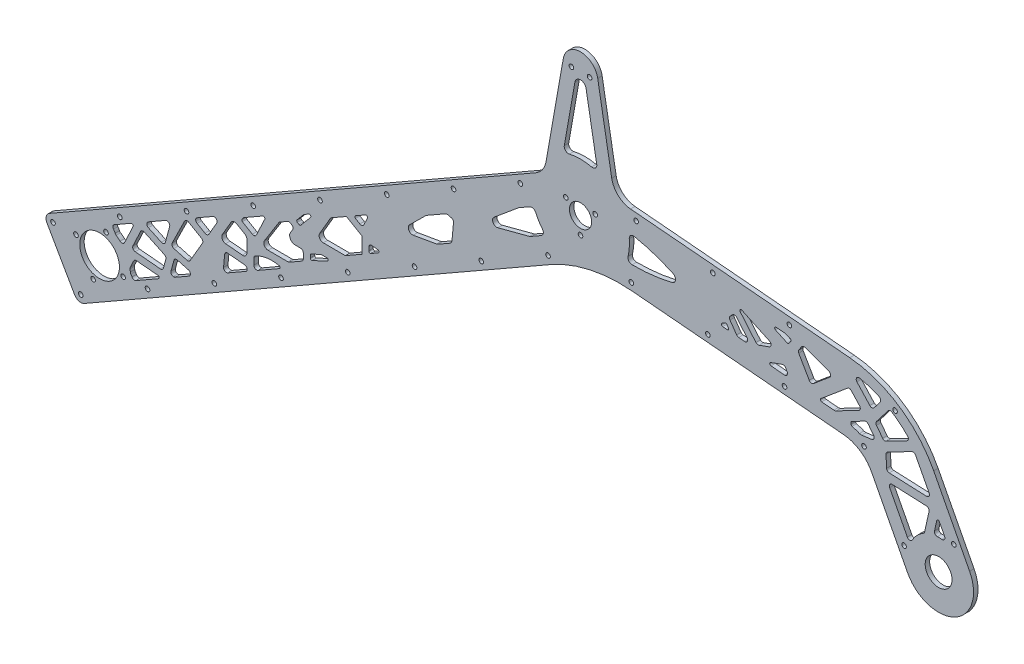
SolidWorks part; units mm, degrees
material "6061-T6 (SS)"
ref_plane "Front Plane" through (0, 0, 0) normal (0, 0, 1) x (1, 0, 0)
ref_plane "Top Plane" through (0, 0, 0) normal (0, 1, 0) x (1, 0, 0)
ref_plane "Right Plane" through (0, 0, 0) normal (1, 0, 0) x (0, 0, -1)
sketch "Reference Sketch" plane through (0, 0, 0) normal (0, 0, 1) x (1, 0, 0)
  line L0 (-343.92, -196.825) -> (0, 0) construction
  line L1 (-243.92, 103.175) -> (356.08, 103.175) construction
  line L2 (-243.92, 103.175) -> (-243.92, 0) construction
  line L3 (-243.92, 0) -> (356.08, 0) construction
  line L4 (356.08, 103.175) -> (356.08, 0) construction
  line L5 (0, 0) -> (256.08, -92.7116) construction
  line L6 (256.08, -92.7116) -> (56.08, -196.825) construction
  line L7 (256.08, -92.7116) -> (456.08, -196.825) construction
  line L8 (-343.92, -196.825) -> (56.08, -196.825) construction
  line L9 (56.08, -196.825) -> (456.08, -196.825) construction
  circle A1 centre (-343.92, -196.825) radius 100 construction
  circle A2 centre (56.08, -196.825) radius 100 construction
  circle A3 centre (456.08, -196.825) radius 100 construction
  circle A4 centre (-343.92, -196.825) radius 16.05 construction
  circle A5 centre (-343.92, -196.825) radius 28.55 construction
  circle A6 centre (-343.92, -196.825) radius 38.55 construction
  circle A7 centre (-343.92, -196.825) radius 33.55 construction
  point P13 (-343.92, -296.825)
  point P14 (556.08, -196.825)
  point P17 (-443.92, -196.825)
  dimension "D3" = 32.1
  dimension "D5" = 200
  dimension "D9" = 57.1
  dimension "D10" = 10
  dimension "D11" = 5
  dimension "D1" = 600
  dimension "D2" = 103.175
  dimension "D4" = 243.92
  dimension "D6" = 125
  dimension "D7" = 400
  dimension "D8" = 1000
  dimension "D12" = 356.08
sketch "Sketch2" plane through (0, 0, 0) normal (0, 0, 1) x (1, 0, 0)
  line L0 (-379.7168, -188.5069) -> (-32.0065, 10.4873)
  line L1 (-354.8814, -231.9028) -> (-21.5627, -41.1449)
  line L2 (-343.92, -196.825) -> (0, 0) construction
  line L3 (-184.3777, -76.7146) -> (-159.5423, -120.1104) construction
  line L4 (-24.685, 20.9013) -> (-12.3101, 91.0831)
  line L5 (12.3101, 91.0831) -> (22.322, 34.3028)
  line L6 (0, 98.4125) -> (0, 112.7) construction
  line L7 (-5.4848, 79.4125) -> (5.4848, 79.4125) construction
  line L8 (5.4848, 79.4125) -> (10.9697, 88.9125) construction
  line L9 (10.9697, 88.9125) -> (5.4848, 98.4125) construction
  line L10 (5.4848, 98.4125) -> (-5.4848, 98.4125) construction
  line L11 (-5.4848, 98.4125) -> (-10.9697, 88.9125) construction
  line L12 (-10.9697, 88.9125) -> (-5.4848, 79.4125) construction
  line L13 (-243.92, 103.175) -> (356.08, 103.175) construction
  line L14 (0, 88.9125) -> (0, 0) construction
  line L15 (35.7868, 21.9646) -> (192.5861, 8.2464)
  line L16 (252.5753, -31.8371) -> (278.2553, -81.1679)
  line L17 (233.9047, -104.2553) -> (208.2247, -54.9245)
  line L18 (36.8237, -28.3172) -> (188.2284, -41.5633)
  line L19 (0, 0) -> (192.5861, -16.8491) construction
  line L21 (-360.8064, -192.2315) -> (-339.3265, -179.9386) construction
  line L22 (-381.5729, -195.33) -> (-361.7045, -230.0467)
  line L23 (256.08, -92.7116) -> (56.08, -196.825) construction
  line L25 (-243.92, 0) -> (356.08, 0) construction
  circle A0 centre (0, 0) radius 7.9375
  circle A1 centre (-343.92, -196.825) radius 14.2
  arc A3 (-12.3101, 91.0831) -> (12.3101, 91.0831) centre (0, 88.9125) cw
  circle A4 centre (0, 88.9125) radius 6.5 construction
  circle A5 centre (-6.5, 88.9125) radius 1.65
  circle A6 centre (6.5, 88.9125) radius 1.65
  circle A7 centre (0, 88.9125) radius 9.5 construction
  arc A8 (252.5753, -31.8371) -> (192.5861, 8.2464) centre (186.0495, -66.4682) ccw
  circle A9 centre (256.08, -92.7116) radius 9.5885
  arc A10 (278.2553, -81.1679) -> (233.9047, -104.2553) centre (256.08, -92.7116) cw
  arc A11 (-21.5627, -41.1449) -> (36.8237, -28.3172) centre (28.1082, -127.9366) cw
  arc A12 (188.2284, -41.5633) -> (208.2247, -54.9245) centre (186.0495, -66.4682) cw
  arc A13 (22.322, 34.3028) -> (35.7868, 21.9646) centre (37.0941, 36.9075) ccw
  arc A14 (-32.0065, 10.4873) -> (-24.685, 20.9013) centre (-39.4572, 23.506) ccw
  circle A17 centre (-343.92, -196.825) radius 17.5 construction
  circle A18 centre (-360.8064, -192.2315) radius 1.65
  circle A19 centre (-339.3265, -179.9386) radius 1.65
  circle A20 centre (-327.0336, -201.4185) radius 1.65
  circle A21 centre (-348.5135, -213.7114) radius 1.65
  arc A27 (-379.7168, -188.5069) -> (-381.5729, -195.33) centre (-377.2333, -192.8465) ccw
  arc A28 (-361.7045, -230.0467) -> (-354.8814, -231.9028) centre (-357.3649, -227.5632) ccw
  circle A29 centre (-343.92, -196.825) radius 33.55 construction
  circle A32 centre (-343.92, -196.825) radius 38.55 construction
  point P16 (-171.96, -98.4125)
  point P64 (-343.92, -196.825)
  dimension "D1" = 15.875
  dimension "D2" = 28.4
  dimension "D3" = 35
  dimension "D5" = 13
  dimension "D6" = 3.3
  dimension "D7" = 6
  dimension "D12" = 50
  dimension "D14" = 100
  dimension "D16" = 15
  dimension "D17" = 5
  dimension "D18" = 25
  dimension "D19" = 3.3
  dimension "D15" = 4
  dimension "D20" = 19.177
  dimension "D4" = 50
  dimension "D8" = 19
  dimension "D9" = 14.2875
  dimension "D10" = 9.525
  dimension "D11" = 10
  dimension "D13" = 50
extrude "Base" add sketch "Sketch2" along normal blind 3.175
sketch "Sketch3" plane through (0, 0, 3.175) normal (0, 0, 1) x (1, 0, 0)
  line L0 (-343.92, -196.825) -> (0, 0) construction
  line L5 (0, 0) -> (197.3986, -17.2701) construction
  line L6 (192.5861, 8.2464) -> (35.7868, 21.9646) construction
  line L7 (0, 0) -> (-23.2167, -36.3305) construction
  line L8 (36.3074, -23.2529) -> (91.0981, -28.0464) construction
  line L9 (36.8237, -28.3172) -> (188.2284, -41.5633) construction
  line L10 (-357.3649, -227.5632) -> (-309.6295, -200.2442) construction
  line L11 (0, 0) -> (36.3074, -23.2529) construction
  line L12 (145.8888, -32.84) -> (188.6641, -36.5824) construction
  line L13 (149.375, 7.0078) -> (192.1504, 3.2654) construction
  line L14 (248.1402, -34.1458) -> (266.894, -70.1715) construction
  line L15 (278.2553, -81.1679) -> (252.5753, -31.8371) construction
  line L16 (212.6598, -52.6158) -> (231.4136, -88.6414) construction
  line L17 (208.2247, -54.9245) -> (233.9047, -104.2553) construction
  line L18 (231.4136, -88.6414) -> (266.894, -70.1715) construction
  circle A0 centre (-357.3649, -227.5632) radius 1.65
  circle A1 centre (-343.92, -196.825) radius 33.55 construction
  arc A2 (-361.7045, -230.0467) -> (-354.8814, -231.9028) centre (-357.3649, -227.5632) ccw construction
  circle A3 centre (-309.6295, -200.2442) radius 1.65
  circle A4 centre (-261.894, -172.9253) radius 1.65
  circle A5 centre (-214.1585, -145.6063) radius 1.65
  circle A6 centre (-166.4231, -118.2874) radius 1.65
  circle A7 centre (-118.6876, -90.9684) radius 1.65
  circle A8 centre (-329.4978, -165.5275) radius 1.65
  circle A9 centre (-377.2333, -192.8465) radius 1.65
  circle A10 centre (-281.7623, -138.2086) radius 1.65
  circle A11 centre (-234.0269, -110.8896) radius 1.65
  circle A12 centre (-186.2914, -83.5707) radius 1.65
  circle A13 centre (-138.5559, -56.2517) radius 1.65
  circle A14 centre (36.3074, -23.2529) radius 1.65
  circle A15 centre (91.0981, -28.0464) radius 1.65
  circle A16 centre (145.8888, -32.84) radius 1.65
  circle A17 centre (149.375, 7.0078) radius 1.65
  circle A18 centre (94.5843, 11.8013) radius 1.65
  circle A19 centre (39.7936, 16.5949) radius 1.65
  circle A20 centre (-70.9521, -63.6495) radius 1.65
  circle A21 centre (-23.2167, -36.3305) radius 1.65
  circle A22 centre (-43.085, -1.6138) radius 1.65
  circle A23 centre (-90.8205, -28.9328) radius 1.65
  arc A24 (188.6641, -36.5824) -> (212.6598, -52.6158) centre (186.0495, -66.4682) cw construction
  arc A25 (208.2247, -54.9245) -> (188.2284, -41.5633) centre (186.0495, -66.4682) ccw construction
  circle A26 centre (202.7166, -41.5241) radius 1.65
  arc A27 (192.1504, 3.2654) -> (248.1402, -34.1458) centre (186.0495, -66.4682) cw construction
  arc A28 (252.5753, -31.8371) -> (192.5861, 8.2464) centre (186.0495, -66.4682) ccw construction
  circle A29 centre (224.9394, -8.2653) radius 1.65
  circle A30 centre (231.4136, -88.6414) radius 1.65
  circle A31 centre (266.894, -70.1715) radius 1.65
  circle A32 centre (256.08, -92.7116) radius 9.5885 construction
  point P82 (263.5112, -63.6495)
  dimension "D1" = 3.3
  dimension "D2" = 8
  dimension "D3" = 5
  dimension "D5" = 3
  dimension "D6" = 15
  dimension "D4" = 55
extrude "Strut Holes" cut sketch "Sketch3" against normal through all
sketch "Sketch6" plane through (0, 0, 3.175) normal (0, 0, 1) x (1, 0, 0)
  line L0 (-317.9371, -199.2378) -> (-301.7593, -189.9792)
  line L1 (-354.8814, -231.9028) -> (-21.5627, -41.1449) construction
  line L2 (-289.845, -183.1607) -> (-279.9388, -177.4914)
  line L3 (-225.0683, -146.089) -> (-215.3943, -140.5526)
  line L4 (-202.4502, -105.5293) -> (-201.3111, -106.1928)
  line L5 (-333.4446, -172.395) -> (-321.3247, -165.4588)
  line L6 (-32.0065, 10.4873) -> (-379.7168, -188.5069) construction
  line L7 (-319.9233, -166.7528) -> (-326.0767, -179.819)
  line L8 (-329.2222, -183.6702) -> (-327.9453, -183.7868) construction
  line L9 (-302.165, -188.1154) -> (-317.5291, -186.7124)
  line L10 (-319.5204, -187.852) -> (-321.9207, -192.9489)
  line L11 (-296.5261, -175.2812) -> (-298.2962, -181.7883)
  line L12 (-300.4079, -183.2551) -> (-318.4265, -181.6097)
  line L13 (-320.054, -178.7659) -> (-314.5879, -167.159)
  line L14 (-311.9264, -166.2018) -> (-297.6038, -172.9468)
  line L15 (-280.4073, -173.8257) -> (-288.2923, -171.6808)
  line L16 (-290.7472, -173.0857) -> (-292.8686, -180.8843)
  line L17 (-296.7252, -151.3805) -> (-309.1621, -158.4982)
  line L18 (-309.0208, -162.0434) -> (-299.7125, -166.427)
  line L19 (-296.9305, -165.1426) -> (-293.8019, -153.6413)
  line L20 (-290.7492, -165.8308) -> (-281.4187, -168.3689)
  line L21 (-279.1655, -167.4456) -> (-270.335, -152.2839)
  line L22 (-271.0566, -149.5491) -> (-280.339, -144.1428)
  line L23 (-283.1398, -144.9875) -> (-292.0185, -163.0173)
  line L24 (-274.1749, -138.475) -> (-262.8296, -131.9821)
  line L25 (-260.108, -134.7245) -> (-265.8054, -144.5068)
  line L26 (-268.5402, -145.2285) -> (-274.188, -141.9391)
  line L27 (-255.2613, -159.7424) -> (-254.4886, -151.2802)
  line L28 (-252.315, -149.4703) -> (-240.2297, -150.5739)
  line L29 (-292.2711, -190.3101) -> (-299.0066, -188.4038) construction
  line L30 (-252.2762, -161.6601) -> (-239.4181, -154.3014)
  line L31 (-249.9491, -129.2039) -> (-256.1296, -139.8156)
  line L32 (-253.8101, -144.313) -> (-241.8428, -145.4058)
  line L33 (-238.5701, -142.4296) -> (-238.5385, -134.1139)
  line L34 (-240.0286, -131.5101) -> (-245.8469, -128.1214)
  line L35 (-233.5719, -142.9305) -> (-233.588, -147.1604)
  line L36 (-241.7536, -124.7193) -> (-234.6398, -128.8625)
  line L37 (-231.8238, -127.9864) -> (-225.7969, -115.1887)
  line L38 (-227.1983, -113.8948) -> (-240.4869, -121.4998)
  line L39 (-215.7001, -112.1928) -> (-226.033, -128.59)
  line L40 (-223.5063, -133.1894) -> (-209.2023, -133.2437)
  line L41 (-208.2012, -132.9795) -> (-199.2535, -127.8588)
  line L42 (-198.247, -126.1305) -> (-198.2324, -122.2852)
  line L43 (-200.2248, -120.2776) -> (-204.0086, -120.2632)
  line L44 (-207.3776, -114.1307) -> (-205.8611, -111.7242)
  line L45 (-206.5466, -108.9297) -> (-207.4931, -108.3784)
  line L46 (-209.4931, -108.3708) -> (-215.0015, -111.5233)
  line L47 (-220.5938, -138.2005) -> (-191.3457, -138.3115) construction
  line L48 (-200.0442, -105.9743) -> (-193.1087, -97.7724)
  line L49 (-194.3691, -96.2588) -> (-197.5103, -98.0565)
  line L50 (-198.0441, -98.501) -> (-202.7105, -104.0195)
  line L51 (-193.2277, -121.0545) -> (-193.2345, -122.8478)
  line L52 (-191.8153, -123.7595) -> (-180.9934, -118.7631)
  line L54 (-192.6468, -120.1504) -> (-185.8787, -117.0256)
  line L55 (-185.0328, -116.8414) -> (-181.4088, -116.8552)
  line L56 (-168.149, -108.9055) -> (-183.9527, -108.8455)
  line L57 (-186.5337, -104.3356) -> (-178.5799, -90.6792)
  line L58 (-178.5799, -90.6792) -> (-167.3868, -84.2735)
  line L59 (-167.3868, -84.2735) -> (-156.3884, -90.6792)
  line L60 (-156.3884, -90.6792) -> (-156.4321, -102.1999)
  line L61 (-156.4321, -102.1999) -> (-168.149, -108.9055)
  line L62 (-178.5799, -90.6792) -> (-168.149, -108.9055) construction
  line L63 (-151.4146, -97.6001) -> (-151.4054, -95.1814)
  line L64 (-149.2236, -93.1973) -> (-145.0326, -93.58)
  line L65 (-144.6268, -95.4437) -> (-149.9179, -98.4719)
  line L66 (-160.8726, -80.5454) -> (-153.7619, -76.4759)
  line L67 (-152.3605, -77.7699) -> (-154.93, -83.2262)
  line L68 (-157.746, -84.1023) -> (-160.8792, -82.2774)
  line L69 (-155.8599, -85.2008) -> (-151.3971, -92.9988) construction
  line L70 (-90.8199, -49.6985) -> (-91.8964, -61.4879)
  line L71 (-93.3939, -63.8188) -> (-101.9943, -68.7409)
  line L72 (-102.9747, -69.0935) -> (-119.6299, -71.9651)
  line L73 (-122.2529, -66.8794) -> (-110.6811, -55.3952)
  line L74 (-110.058, -54.9208) -> (-96.7247, -47.2901)
  line L75 (-94.4471, -46.9991) -> (-92.2866, -47.5868)
  line L76 (-102.4534, -69.0036) -> (-110.4008, -55.117) construction
  line L78 (-28.0968, -26.4494) -> (-35.8254, -30.8725)
  line L79 (-36.5501, -31.1694) -> (-59.134, -37.129)
  line L80 (-61.819, -31.9228) -> (-44.3172, -17.3499)
  line L81 (-43.8877, -17.0516) -> (-36.2746, -12.6946)
  line L82 (-44.1155, -17.182) -> (-36.1682, -31.0687) construction
  line L83 (-11.5997, 37.5245) -> (-3.9861, 80.7029)
  line L84 (3.9861, 80.7029) -> (11.5997, 37.5245)
  line L85 (22.322, 34.3028) -> (12.3101, 91.0831) construction
  line L86 (-12.3101, 91.0831) -> (-24.685, 20.9013) construction
  line L87 (192.5861, 8.2464) -> (35.7868, 21.9646) construction
  line L88 (36.8237, -28.3172) -> (188.2284, -41.5633) construction
  line L89 (-227.1773, -153.057) -> (-233.9128, -151.1507) construction
  line L90 (246.076, -72.9136) -> (249.254, -58.5784)
  line L91 (247.3887, -56.1475) -> (222.9622, -55.081)
  line L92 (221.1009, -58.0026) -> (233.7353, -82.273)
  line L93 (208.2247, -54.9245) -> (233.9047, -104.2553) construction
  line L94 (253.1337, -68.7997) -> (254.752, -61.5)
  line L95 (256.6153, -61.2547) -> (260.3456, -68.4206)
  line L96 (278.2553, -81.1679) -> (252.5753, -31.8371) construction
  line L97 (249.3108, -47.2228) -> (239.5975, -28.5637)
  line L98 (236.9, -27.7132) -> (219.5656, -36.7369)
  line L99 (218.491, -38.5982) -> (218.8608, -47.0688)
  line L100 (220.7717, -48.9796) -> (247.4495, -50.1444)
  line L101 (233.4135, -22.7639) -> (218.6181, -30.4658)
  line L102 (216.1079, -29.9093) -> (211.6718, -24.1281)
  line L103 (211.6718, -21.693) -> (220.0072, -10.8302)
  line L104 (209.6166, -31.3057) -> (205.7463, -26.2618)
  line L105 (203.2361, -25.7053) -> (194.0101, -30.5081)
  line L106 (193.4718, -31.3951) -> (193.4718, -32.4967)
  line L107 (201.069, -35.4569) -> (208.2909, -34.5061)
  line L108 (214.3031, -8.4078) -> (209.9577, -14.0708)
  line L109 (197.6887, -4.156) -> (206.8964, -14.2045)
  line L110 (193.6814, -11.6243) -> (199.5455, -18.0239)
  line L111 (198.9945, -21.1491) -> (182.8075, -29.5754)
  line L112 (181.1608, -29.903) -> (172.4826, -29.1438)
  line L113 (171.927, -27.3815) -> (190.9213, -11.4434)
  line L114 (178.1992, -11.0225) -> (166.5918, -20.7623)
  line L115 (163.5742, -20.2302) -> (156.048, -7.1944)
  line L116 (156.1417, -5.0472) -> (158.1885, -2.1242)
  line L117 (160.5108, -1.3919) -> (177.5977, -7.611)
  line L118 (146.6448, -20.9077) -> (147.747, -22.8167)
  line L119 (145.8406, -25.8091) -> (136.23, -24.9682)
  line L120 (135.9751, -23.0324) -> (144.2287, -20.0283)
  line L121 (134.9743, -13.819) -> (127.6718, -16.4769)
  line L122 (125.4557, -15.8831) -> (114.1985, -2.4673)
  line L123 (115.3872, -0.9182) -> (135.1355, -10.127)
  line L124 (139.4306, -1.096) -> (147.8318, -5.0136)
  line L125 (149.0736, -4.6809) -> (150.4259, -2.7496)
  line L126 (149.9488, -1.2363) -> (146.0985, 0.1651)
  line L127 (145.3339, 0.3346) -> (139.9404, 0.8065)
  line L128 (111.6605, -7.2212) -> (119.0455, -16.0223)
  line L129 (117.3391, -19.3002) -> (113.1162, -18.9308)
  line L130 (111.6522, -18.0855) -> (106.8775, -11.2665)
  line L131 (107.1016, -8.7052) -> (108.7142, -7.0926)
  line L132 (104.7039, -15.1361) -> (105.7554, -16.6377)
  line L133 (104.8491, -18.2075) -> (101.6773, -17.93)
  line L134 (101.2644, -16.0678) -> (103.3847, -14.8436)
  line L135 (-225.0683, -146.089) -> (-230.5959, -149.2525)
  line L136 (-233.5893, -147.5091) -> (-233.588, -147.1604)
  arc A0 (-320.7312, -198.3723) -> (-321.5152, -197.1118) centre (-327.0336, -201.4185) ccw
  arc A1 (-291.1568, -183.3993) -> (-291.2348, -183.3872) centre (-292.2711, -190.3101) ccw
  arc A2 (-225.7665, -146.2006) -> (-231.9116, -147.9008) centre (-227.1773, -153.057) ccw construction
  arc A4 (-321.937, -195.96) -> (-322.0953, -194.053) centre (-343.92, -196.825) ccw
  arc A5 (-332.8179, -177.3623) -> (-333.9791, -175.4215) centre (-339.3265, -179.9386) ccw
  arc A6 (-329.2222, -180.455) -> (-332.0384, -178.3094) centre (-343.92, -196.825) ccw
  arc A8 (-232.5183, -141.1762) -> (-215.6911, -138.7049) centre (-220.6887, -163.2003) cw
  arc A9 (-241.9747, -123.1658) -> (-241.1717, -122.1478) centre (-247.0456, -118.3403) ccw
  arc A10 (-32.0383, -14.0906) -> (-27.2511, -21.9631) centre (0, 0) ccw
  arc A11 (-256.1296, -139.8156) -> (-253.8101, -144.313) centre (-253.5373, -141.3254) ccw
  arc A12 (-226.033, -128.59) -> (-223.5063, -133.1894) centre (-223.4949, -130.1894) ccw
  arc A13 (-183.9527, -108.8455) -> (-186.5337, -104.3356) centre (-183.9413, -105.8455) cw
  arc A14 (-119.6299, -71.9651) -> (-122.2529, -66.8794) centre (-120.1396, -69.0087) cw
  arc A15 (-59.134, -37.129) -> (-61.819, -31.9228) centre (-59.8994, -34.2283) cw
  arc A16 (-7.9627, 34.0822) -> (7.9627, 34.0822) centre (0, 0) cw
  arc A17 (-3.9861, 80.7029) -> (3.9861, 80.7029) centre (0, 80) cw
  arc A18 (34.8636, 3.0867) -> (34.0029, -8.2948) centre (0, 0) cw
  arc A19 (38.4335, 6.2944) -> (66.0977, -2.7713) centre (15.1723, -111.4295) cw
  arc A20 (66.0977, -2.7713) -> (65.4856, -8.7407) centre (64.749, -5.6491) cw
  arc A21 (36.898, -12.0057) -> (65.4856, -8.7407) centre (37.6733, 107.9918) ccw
  arc A22 (245.141, -74.2025) -> (237.26, -82.3165) centre (256.08, -92.7116) ccw
  arc A23 (258.3595, -71.3328) -> (255.1708, -71.2308) centre (256.08, -92.7116) ccw
  arc A24 (222.6875, -10.3732) -> (233.9189, -19.5905) centre (186.0495, -66.4682) cw
  arc A25 (252.5753, -31.8371) -> (192.5861, 8.2464) centre (186.0495, -66.4682) ccw construction
  arc A26 (194.2312, -33.4673) -> (199.4914, -35.2382) centre (186.0495, -66.4682) cw
  arc A27 (208.2247, -54.9245) -> (188.2284, -41.5633) centre (186.0495, -66.4682) ccw construction
  arc A28 (213.5369, -5.3663) -> (199.5667, -0.8459) centre (186.0495, -66.4682) ccw
  arc A29 (218.8608, -47.0688) -> (220.7717, -48.9796) centre (220.8589, -46.9815) ccw
  arc A30 (239.5975, -28.5637) -> (236.9, -27.7132) centre (237.8235, -29.4872) ccw
  arc A31 (219.5656, -36.7369) -> (218.491, -38.5982) centre (220.4891, -38.5109) ccw
  arc A32 (127.6718, -16.4769) -> (125.4557, -15.8831) centre (126.9878, -14.5975) cw
  arc A33 (-240.4869, -121.4998) -> (-241.1717, -122.1478) centre (-239.4934, -123.2356) ccw
  arc A34 (-234.6398, -128.8625) -> (-231.8238, -127.9864) centre (-233.6332, -127.1343) ccw
  arc A35 (-233.5719, -142.9305) -> (-232.5183, -141.1762) centre (-231.5719, -142.9381) cw
  arc A36 (-317.9371, -199.2378) -> (-320.7312, -198.3723) centre (-318.9305, -197.5019) cw
  arc A37 (-321.937, -195.96) -> (-321.5152, -197.1118) centre (-319.9386, -195.8813) ccw
  arc A38 (-321.9207, -192.9489) -> (-322.0953, -194.053) centre (-320.1113, -193.801) ccw
  arc A39 (-317.5291, -186.7124) -> (-319.5204, -187.852) centre (-317.711, -188.7042) ccw
  arc A42 (-332.8179, -177.3623) -> (-332.0384, -178.3094) centre (-330.9583, -176.6261) ccw
  arc A43 (-333.4446, -172.395) -> (-333.9791, -175.4215) centre (-332.4512, -174.1309) ccw
  arc A44 (-318.4265, -181.6097) -> (-320.054, -178.7659) centre (-318.2446, -179.618) cw
  arc A45 (-298.2962, -181.7883) -> (-300.4079, -183.2551) centre (-300.226, -181.2634) cw
  arc A46 (-289.845, -183.1607) -> (-291.1568, -183.3993) centre (-290.8384, -181.4248) cw
  arc A47 (-292.8686, -180.8843) -> (-291.2348, -183.3872) centre (-290.9387, -181.4092) ccw
  arc A48 (-280.4073, -173.8257) -> (-279.9388, -177.4914) centre (-280.9322, -175.7556) cw
  arc A49 (-288.2923, -171.6808) -> (-290.7472, -173.0857) centre (-288.8173, -173.6107) ccw
  arc A50 (-296.5261, -175.2812) -> (-297.6038, -172.9468) centre (-298.456, -174.7562) ccw
  arc A51 (-314.5879, -167.159) -> (-311.9264, -166.2018) centre (-312.7785, -168.0112) cw
  arc A52 (-309.1621, -158.4982) -> (-309.0208, -162.0434) centre (-308.1687, -160.234) ccw
  arc A53 (-296.7252, -151.3805) -> (-293.8019, -153.6413) centre (-295.7318, -153.1164) cw
  arc A54 (-299.7125, -166.427) -> (-296.9305, -165.1426) centre (-298.8604, -164.6177) ccw
  arc A55 (-290.7492, -165.8308) -> (-292.0185, -163.0173) centre (-290.2242, -163.9009) cw
  arc A56 (-281.4187, -168.3689) -> (-279.1655, -167.4456) centre (-280.8937, -166.439) ccw
  arc A57 (-270.335, -152.2839) -> (-271.0566, -149.5491) centre (-272.0632, -151.2774) ccw
  arc A58 (-280.339, -144.1428) -> (-283.1398, -144.9875) centre (-281.3456, -145.8711) ccw
  arc A59 (-274.1749, -138.475) -> (-274.188, -141.9391) centre (-273.1814, -140.2108) ccw
  arc A60 (-265.8054, -144.5068) -> (-268.5402, -145.2285) centre (-267.5336, -143.5003) cw
  arc A61 (-254.4886, -151.2802) -> (-252.315, -149.4703) centre (-252.4969, -151.462) cw
  arc A62 (-255.2613, -159.7424) -> (-252.2762, -161.6601) centre (-253.2696, -159.9243) ccw
  arc A63 (-239.4181, -154.3014) -> (-240.2297, -150.5739) centre (-240.4115, -152.5656) ccw
  arc A64 (-262.8296, -131.9821) -> (-260.108, -134.7245) centre (-261.8362, -133.718) cw
  arc A65 (-209.2023, -133.2437) -> (-208.2012, -132.9795) centre (-209.1947, -131.2437) ccw
  arc A66 (-215.0015, -111.5233) -> (-215.7001, -112.1928) centre (-214.0081, -113.2591) ccw
  arc A67 (-207.4931, -108.3784) -> (-209.4931, -108.3708) centre (-208.4997, -110.1067) ccw
  arc A68 (-205.8611, -111.7242) -> (-206.5466, -108.9297) centre (-207.5531, -110.658) ccw
  arc A69 (-204.0086, -120.2632) -> (-207.3776, -114.1307) centre (-203.9934, -116.2633) cw
  arc A70 (-198.2324, -122.2852) -> (-200.2248, -120.2776) centre (-200.2323, -122.2776) ccw
  arc A71 (-199.2535, -127.8588) -> (-198.247, -126.1305) centre (-200.2469, -126.1229) ccw
  arc A72 (-185.8787, -117.0256) -> (-185.0328, -116.8414) centre (-185.0404, -118.8414) cw
  arc A73 (-197.5103, -98.0565) -> (-198.0441, -98.501) centre (-196.5169, -99.7924) ccw
  arc A74 (-151.4054, -95.1814) -> (-149.2236, -93.1973) centre (-149.4054, -95.189) cw
  arc A75 (-154.93, -83.2262) -> (-157.746, -84.1023) centre (-156.7394, -82.374) cw
  arc A76 (-90.8199, -49.6985) -> (-92.2866, -47.5868) centre (-92.8116, -49.5167) ccw
  arc A77 (111.6605, -7.2212) -> (108.7142, -7.0926) centre (110.1284, -8.5068) ccw
  arc A78 (106.8775, -11.2665) -> (107.1016, -8.7052) centre (108.5158, -10.1194) cw
  arc A79 (113.1162, -18.9308) -> (111.6522, -18.0855) centre (113.2905, -16.9384) cw
  arc A80 (119.0455, -16.0223) -> (117.3391, -19.3002) centre (117.5134, -17.3078) cw
  arc A81 (134.9743, -13.819) -> (135.1355, -10.127) centre (134.2903, -11.9396) ccw
  arc A82 (146.6448, -20.9077) -> (144.2287, -20.0283) centre (144.9128, -21.9077) ccw
  arc A83 (147.747, -22.8167) -> (145.8406, -25.8091) centre (146.0149, -23.8167) cw
  arc A84 (156.048, -7.1944) -> (156.1417, -5.0472) centre (157.78, -6.1944) cw
  arc A85 (158.1885, -2.1242) -> (160.5108, -1.3919) centre (159.8268, -3.2713) cw
  arc A86 (178.1992, -11.0225) -> (177.5977, -7.611) centre (176.9136, -9.4904) ccw
  arc A87 (166.5918, -20.7623) -> (163.5742, -20.2302) centre (165.3062, -19.2302) cw
  arc A88 (193.6814, -11.6243) -> (190.9213, -11.4434) centre (192.2068, -12.9755) ccw
  arc A89 (199.5455, -18.0239) -> (198.9945, -21.1491) centre (198.071, -19.375) cw
  arc A90 (209.9577, -14.0708) -> (206.8964, -14.2045) centre (208.371, -12.8533) cw
  arc A91 (213.5369, -5.3663) -> (214.3031, -8.4078) centre (212.7164, -7.1903) cw
  arc A92 (233.9189, -19.5905) -> (233.4135, -22.7639) centre (232.49, -20.9899) cw
  arc A93 (222.6875, -10.3732) -> (220.0072, -10.8302) centre (221.5939, -12.0477) ccw
  arc A94 (211.6718, -24.1281) -> (211.6718, -21.693) centre (213.2585, -22.9105) cw
  arc A95 (218.6181, -30.4658) -> (216.1079, -29.9093) centre (217.6946, -28.6918) cw
  arc A96 (205.7463, -26.2618) -> (203.2361, -25.7053) centre (204.1595, -27.4793) ccw
  arc A97 (209.6166, -31.3057) -> (208.2909, -34.5061) centre (208.0299, -32.5232) cw
  arc A98 (246.076, -72.9136) -> (245.141, -74.2025) centre (244.1234, -72.4807) cw
  arc A99 (249.254, -58.5784) -> (247.3887, -56.1475) centre (247.3014, -58.1456) ccw
  arc A100 (222.9622, -55.081) -> (221.1009, -58.0026) centre (222.8749, -57.0791) ccw
  arc A101 (233.7353, -82.273) -> (237.26, -82.3165) centre (235.5093, -81.3495) ccw
  arc A102 (260.3456, -68.4206) -> (258.3595, -71.3328) centre (258.5716, -69.344) cw
  arc A103 (253.1337, -68.7997) -> (255.1708, -71.2308) centre (255.0863, -69.2326) ccw
  arc A104 (249.3108, -47.2228) -> (247.4495, -50.1444) centre (247.5367, -48.1463) cw
  arc A105 (199.5667, -0.8459) -> (197.6887, -4.156) centre (199.1632, -2.8048) ccw
  arc A106 (-215.6911, -138.7049) -> (-215.3943, -140.5526) centre (-215.891, -139.6847) cw
  arc A107 (-301.7593, -189.9792) -> (-302.165, -188.1154) centre (-302.256, -189.1113) ccw
  arc A108 (-321.3247, -165.4588) -> (-319.9233, -166.7528) centre (-320.828, -166.3267) cw
  arc A109 (-225.7969, -115.1887) -> (-227.1983, -113.8948) centre (-226.7016, -114.7627) ccw
  arc A110 (-241.7536, -124.7193) -> (-241.9747, -123.1658) centre (-241.2503, -123.8551) cw
  arc A111 (-225.7665, -146.2006) -> (-225.0683, -146.089) centre (-225.565, -145.2211) ccw construction
  arc A112 (-233.588, -147.1604) -> (-231.9116, -147.9008) centre (-232.588, -147.1642) ccw construction
  arc A113 (-202.4502, -105.5293) -> (-202.7105, -104.0195) centre (-201.9469, -104.6652) cw
  arc A114 (-201.3111, -106.1928) -> (-200.0442, -105.9743) centre (-200.8078, -105.3286) ccw
  arc A115 (-193.2277, -121.0545) -> (-192.6468, -120.1504) centre (-192.2277, -121.0583) cw
  arc A116 (-193.2345, -122.8478) -> (-191.8153, -123.7595) centre (-192.2345, -122.8516) ccw
  arc A117 (-193.1087, -97.7724) -> (-194.3691, -96.2588) centre (-193.8723, -97.1267) ccw
  arc A118 (-180.9934, -118.7631) -> (-181.4088, -116.8552) centre (-181.4126, -117.8552) ccw
  arc A119 (-153.7619, -76.4759) -> (-152.3605, -77.7699) centre (-153.2652, -77.3438) cw
  arc A120 (-160.8726, -80.5454) -> (-160.8792, -82.2774) centre (-160.3759, -81.4133) ccw
  arc A121 (-151.4146, -97.6001) -> (-149.9179, -98.4719) centre (-150.4146, -97.6039) ccw
  arc A122 (-145.0326, -93.58) -> (-144.6268, -95.4437) centre (-145.1235, -94.5758) cw
  arc A123 (101.6773, -17.93) -> (101.2644, -16.0678) centre (101.7644, -16.9338) cw
  arc A124 (104.7039, -15.1361) -> (103.3847, -14.8436) centre (103.8847, -15.7096) ccw
  arc A125 (105.7554, -16.6377) -> (104.8491, -18.2075) centre (104.9362, -17.2113) cw
  arc A126 (114.1985, -2.4673) -> (115.3872, -0.9182) centre (114.9646, -1.8245) cw
  arc A127 (136.23, -24.9682) -> (135.9751, -23.0324) centre (136.3171, -23.972) cw
  arc A128 (139.4306, -1.096) -> (139.9404, 0.8065) centre (139.8532, -0.1897) cw
  arc A129 (172.4826, -29.1438) -> (171.927, -27.3815) centre (172.5698, -28.1476) cw
  arc A130 (194.0101, -30.5081) -> (193.4718, -31.3951) centre (194.4718, -31.3951) ccw
  arc A131 (193.4718, -32.4967) -> (194.2312, -33.4673) centre (194.4718, -32.4967) ccw
  arc A132 (254.752, -61.5) -> (256.6153, -61.2547) centre (255.7283, -61.7164) cw
  arc A133 (146.0985, 0.1651) -> (145.3339, 0.3346) centre (145.0724, -2.654) ccw
  arc A134 (199.4914, -35.2382) -> (201.069, -35.4569) centre (200.6774, -32.4826) ccw
  arc A135 (182.8075, -29.5754) -> (181.1608, -29.903) centre (181.4223, -26.9144) cw
  arc A136 (-7.9627, 34.0822) -> (-11.5997, 37.5245) centre (-8.6452, 37.0035) cw
  arc A137 (7.9627, 34.0822) -> (11.5997, 37.5245) centre (8.6452, 37.0035) ccw
  arc A138 (34.8636, 3.0867) -> (38.4335, 6.2944) centre (37.8519, 3.3513) cw
  arc A139 (34.0029, -8.2948) -> (36.898, -12.0057) centre (36.9174, -9.0058) ccw
  arc A140 (-35.8254, -30.8725) -> (-36.5501, -31.1694) centre (-37.3155, -28.2687) cw
  arc A141 (-44.3172, -17.3499) -> (-43.8877, -17.0516) centre (-42.3976, -19.6554) cw
  arc A142 (-32.0383, -14.0906) -> (-36.2746, -12.6946) centre (-34.7845, -15.2984) ccw
  arc A143 (-27.2511, -21.9631) -> (-28.0968, -26.4494) centre (-29.5869, -23.8456) cw
  arc A144 (-96.7247, -47.2901) -> (-94.4471, -46.9991) centre (-95.2346, -49.8939) cw
  arc A145 (-91.8964, -61.4879) -> (-93.3939, -63.8188) centre (-94.884, -61.2151) cw
  arc A146 (-110.6811, -55.3952) -> (-110.058, -54.9208) centre (-108.5679, -57.5245) cw
  arc A147 (-101.9943, -68.7409) -> (-102.9747, -69.0935) centre (-103.4845, -66.1371) cw
  arc A148 (-249.9491, -129.2039) -> (-245.8469, -128.1214) centre (-247.3568, -130.7138) cw
  arc A149 (-238.5385, -134.1139) -> (-240.0286, -131.5101) centre (-241.5385, -134.1025) ccw
  arc A150 (-241.8428, -145.4058) -> (-238.5701, -142.4296) centre (-241.57, -142.4182) ccw
  arc A151 (150.4259, -2.7496) -> (149.9488, -1.2363) centre (149.6067, -2.176) ccw
  arc A152 (147.8318, -5.0136) -> (149.0736, -4.6809) centre (148.2544, -4.1073) ccw
  arc A153 (-329.2222, -180.455) -> (-326.0767, -179.819) centre (-327.8861, -178.9669) ccw
  arc A154 (-230.5959, -149.2525) -> (-233.5893, -147.5091) centre (-231.5893, -147.5167) cw
  point P110 (-258.4996, -143.8848)
  point P113 (-228.9184, -133.1688)
  point P143 (34.9003, -2.6394)
  point P203 (218.9408, -48.8997)
  point P206 (238.674, -26.7897)
  point P211 (126.3559, -16.9559)
  point P214 (-240.9361, -121.7569)
  point P217 (-232.7537, -129.961)
  point P220 (-233.5675, -141.7728)
  point P229 (-318.9237, -186.5851)
  point P232 (-327.9453, -183.7868)
  point P235 (-326.0754, -183.9575)
  point P240 (-335.9304, -173.8176)
  point P247 (-290.5028, -183.5371)
  point P252 (-275.7482, -175.0931)
  point P255 (-290.2222, -171.1558)
  point P262 (-312.4966, -160.4065)
  point P265 (-292.5345, -148.9822)
  point P268 (-297.5562, -167.4426)
  point P271 (-293.0903, -165.1939)
  point P278 (-282.1923, -143.0634)
  point P281 (-277.1814, -140.1957)
  point P288 (-255.6107, -163.5684)
  point P294 (-256.3514, -128.2747)
  point P297 (-208.6664, -133.2457)
  point P300 (-215.4343, -111.7709)
  point P303 (-208.4909, -107.7973)
  point P308 (-211.2248, -120.2358)
  point P311 (-198.2248, -120.2852)
  point P314 (-198.2513, -127.2852)
  point P329 (110.2575, -5.5492)
  point P334 (112.1872, -18.8495)
  point P337 (122.1491, -19.721)
  point P340 (139.5116, -12.1676)
  point P345 (149.6679, -26.1439)
  point P350 (159.0687, -0.8671)
  point P353 (180.8529, -8.7958)
  point P356 (164.7659, -22.2944)
  point P363 (208.5067, -15.9618)
  point P366 (215.8118, -6.4415)
  point P369 (235.7568, -21.544)
  point P374 (210.7376, -22.9105)
  point P377 (217.1296, -31.2407)
  point P380 (204.7246, -24.9304)
  point P383 (211.7254, -34.054)
  point P390 (219.5014, -54.9299)
  point P393 (235.6626, -85.9753)
  point P396 (262.2729, -72.1228)
  point P401 (250.9103, -50.2955)
  point P406 (-213.2581, -139.3301)
  point P412 (-318.5721, -163.8835)
  point P415 (-224.4456, -112.3194)
  point P420 (-225.4089, -146.284)
  point P423 (-233.5998, -150.2728)
  point P426 (-203.48, -104.9295)
  point P431 (-193.2252, -120.4175)
  point P434 (-193.2404, -124.4175)
  point P437 (-189.4469, -93.4418)
  point P440 (-176.8981, -116.8723)
  point P447 (-151.4212, -99.3322)
  point P450 (-141.8741, -93.8684)
  point P453 (98.5177, -17.6536)
  point P458 (106.9854, -18.3944)
  point P463 (131.7364, -24.5751)
  point P468 (170.0776, -28.9333)
  point P471 (193.4718, -30.7883)
  point P474 (193.4718, -33.2883)
  point P477 (255.3467, -58.8176)
  point P484 (182.0319, -29.9792)
  point P491 (34.2849, 7.0387)
  point P494 (32.91, -11.9136)
  point P505 (-24.8853, -24.6115)
  point P508 (-95.6462, -46.6729)
  point P511 (-92.0384, -63.0431)
  point P524 (-238.5825, -145.7035)
  point P527 (151.1734, -1.682)
  point P530 (148.5923, -5.3682)
  dimension "D1" = 14
  dimension "D2" = 10
  dimension "D3" = 2
  dimension "D5" = 22
  dimension "D6" = 9
  dimension "D12" = 5
  dimension "D19" = 7
  dimension "D31" = 7
  dimension "D40" = 25
  dimension "D44" = 19
  dimension "D62" = 5
  dimension "D92" = 35
  dimension "D96" = 3
  dimension "D97" = 10
  dimension "D100" = 15
  dimension "D104" = 30
  dimension "D105" = 120
  dimension "D107" = 43
  dimension "D116" = 65
  dimension "D117" = 8
  dimension "D127" = 9
  dimension "D128" = 6
  dimension "D171" = 2
  dimension "D172" = 1
  dimension "D173" = 3
  dimension "D174" = 1
  dimension "D175" = 4
  dimension "D176" = 2
  dimension "D177" = 123.1958
  dimension "D183" = 7
  dimension "D184" = 2
  dimension "D7" = 35
  dimension "D8" = 35
  dimension "D9" = 20
  dimension "D10" = 22
  dimension "D11" = 20
  dimension "D13" = 5
  dimension "D14" = 45
  dimension "D15" = 45
  dimension "D16" = 17
  dimension "D17" = 15
  dimension "D18" = 5
  dimension "D20" = 55
  dimension "D21" = 5
  dimension "D22" = 45
  dimension "D23" = 23
  dimension "D24" = 34
  dimension "D25" = 60
  dimension "D26" = 5
  dimension "D27" = 5
  dimension "D28" = 5
  dimension "D29" = 30
  dimension "D30" = 24
  dimension "D32" = 55
  dimension "D33" = 35
  dimension "D34" = 25
  dimension "D35" = 5
  dimension "D36" = 6
  dimension "D37" = 60
  dimension "D38" = 5
  dimension "D39" = 20
  dimension "D41" = 11
  dimension "D42" = 35
  dimension "D43" = 60
  dimension "D45" = 19.5
  dimension "D46" = 5
  dimension "D47" = 5
  dimension "D48" = 30
  dimension "D49" = 5
  dimension "D50" = 14
  dimension "D51" = 13
  dimension "D52" = 8.5
  dimension "D53" = 60
  dimension "D54" = 12
  dimension "D55" = 7
  dimension "D56" = 22
  dimension "D57" = 28
  dimension "D58" = 60
  dimension "D59" = 15
  dimension "D60" = 8
  dimension "D61" = 13
  dimension "D63" = 12
  dimension "D64" = 20
  dimension "D65" = 5
  dimension "D66" = 65
  dimension "D67" = 25
  dimension "2" = 18
  dimension "D68" = 8
  dimension "D69" = 4
  dimension "D70" = 14
  dimension "D71" = 15
  dimension "D72" = 13.5
  dimension "D73" = 60
  dimension "D74" = 60
  dimension "D75" = 8
  dimension "D76" = 5
  dimension "D77" = 35
  dimension "D78" = 0.5076
  dimension "D79" = 5
  dimension "D80" = 11
  dimension "D81" = 35
  dimension "D82" = 16
  dimension "D83" = 18
  dimension "D84" = 55
  dimension "D85" = 45
  dimension "D86" = 20
  dimension "D87" = 15
  dimension "D88" = 12
  dimension "D89" = 17
  dimension "D90" = 16
  dimension "D91" = 18
  dimension "D93" = 15
  dimension "D94" = 10
  dimension "D95" = 13
  dimension "D98" = 10
  dimension "D99" = 80
  dimension "D101" = 16
  dimension "D102" = 22
  dimension "D103" = 22
  dimension "D106" = 7
  dimension "D108" = 10
  dimension "D109" = 40
  dimension "D110" = 10
  dimension "D111" = 6
  dimension "D112" = 60
  dimension "D113" = 35
  dimension "D114" = 15
  dimension "D115" = 6
  dimension "D118" = 26.5
  dimension "D119" = 6
  dimension "D120" = 85
  dimension "D121" = 85
  dimension "D122" = 32
  dimension "D123" = 21
  dimension "D124" = 80
  dimension "D125" = 75
  dimension "D126" = 6
  dimension "D129" = 10.5
  dimension "D130" = 80
  dimension "D131" = 12
  dimension "D132" = 8
  dimension "D133" = 6
  dimension "D134" = 2.5
  dimension "D135" = 100
  dimension "D136" = 11.5
  dimension "D137" = 60
  dimension "D138" = 11
  dimension "D139" = 45
  dimension "D140" = 12
  dimension "D141" = 8.5
  dimension "D142" = 12
  dimension "D143" = 18
  dimension "D144" = 80
  dimension "D145" = 21
  dimension "D146" = 60
  dimension "D147" = 60
  dimension "D148" = 15
  dimension "D149" = 12
  dimension "D150" = 18
  dimension "D151" = 25
  dimension "D152" = 9
  dimension "D153" = 12
  dimension "D154" = 6
  dimension "D155" = 15
  dimension "D156" = 20
  dimension "D157" = 10
  dimension "D158" = 13.5
  dimension "D159" = 4.5
  dimension "D160" = 45
  dimension "D161" = 14
  dimension "D162" = 5
  dimension "D163" = 10
  dimension "D164" = 16
  dimension "D165" = 50
  dimension "D166" = 18.5
  dimension "D167" = 50
  dimension "D168" = 4
  dimension "D169" = 8.5
  dimension "D170" = 35
  dimension "D178" = 124.6776
  dimension "D179" = 5
  dimension "D180" = 124.6776
  dimension "D181" = 5
  dimension "D182" = 36.4942
extrude "Lightening Holes" cut sketch "Sketch6" against normal through all
sketch "Sketch7" plane through (0, 0, 3.175) normal (0, 0, 1) x (1, 0, 0)
  circle A0 centre (-10.5, 6.0622) radius 1.65
  circle A1 centre (10.5, 6.0622) radius 1.65
  circle A2 centre (0, -12.1244) radius 1.65
  point P8 (0, 0)
  dimension "D1" = 3.3
  dimension "D3" = 21
  dimension "D2" = 3
extrude "Cut-Extrude1" cut sketch "Sketch7" against normal through all
